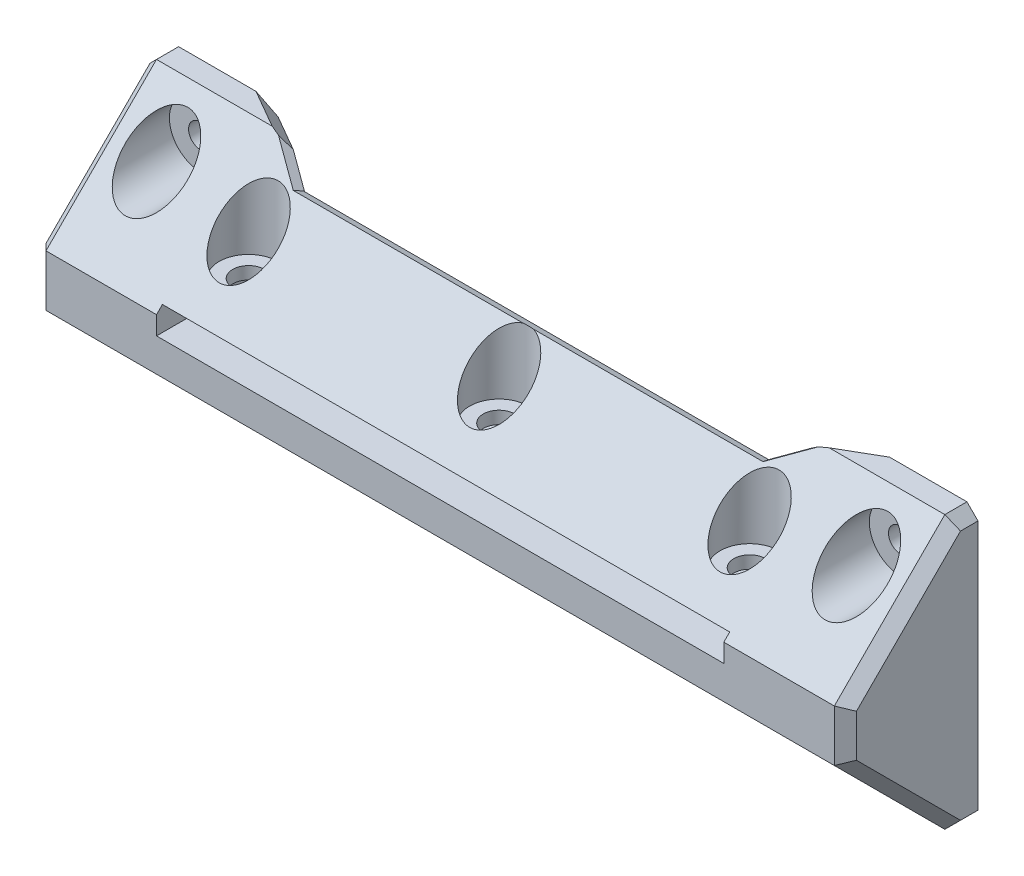
SolidWorks part; units mm, degrees
ref_plane "Front Plane" through (0, 0, 0) normal (0, 0, 1) x (1, 0, 0)
ref_plane "Top Plane" through (0, 0, 0) normal (0, 1, 0) x (1, 0, 0)
ref_plane "Right Plane" through (0, 0, 0) normal (1, 0, 0) x (0, 0, -1)
sketch "Sketch1" plane through (0, 0, 0) normal (0, 0, 1) x (1, 0, 0)
  line L1 (-102.5, 51) -> (7.5, 51)
  line L2 (-102.5, 51) -> (-102.5, 14)
  line L3 (-102.5, 14) -> (7.5, 14)
  line L4 (7.5, 51) -> (7.5, 14)
  line L8 (-9.0001, 36.8) -> (-85.9999, 36.8)
  line L9 (-9.0001, 36.8) -> (-9.0001, 33.5)
  line L10 (-9.0001, 33.5) -> (-85.9999, 33.5)
  line L11 (-85.9999, 36.8) -> (-85.9999, 33.5)
  line L12 (-10.0001, 34) -> (-13.5, 34) construction
  line L14 (-84.9999, 37) -> (-84.9999, 34) construction
  line L15 (-10.0001, 37) -> (-10.0001, 34) construction
  line L16 (-78.5, 37) -> (-16.5, 37) construction
  line L17 (7.5, 29.6539) -> (7.5, 84.2824) construction
  line L18 (-102.5, 18.739) -> (-102.5, -23.6652) construction
  arc A0 (-95, 46.65) -> (-95, 43.35) centre (-95, 45) ccw construction
  arc A1 (-95, 43.35) -> (-95, 46.65) centre (-95, 45) ccw construction
  arc A2 (0, 46.65) -> (0, 43.35) centre (0, 45) ccw construction
  arc A3 (0, 43.35) -> (0, 46.65) centre (0, 45) ccw construction
  arc A4 (0, 21.65) -> (0, 18.35) centre (0, 20) ccw construction
  arc A5 (0, 18.35) -> (0, 21.65) centre (0, 20) ccw construction
  arc A6 (-95, 21.65) -> (-95, 18.35) centre (-95, 20) ccw construction
  arc A7 (-95, 18.35) -> (-95, 21.65) centre (-95, 20) ccw construction
  arc A8 (-95, 18.35) -> (-95, 21.65) centre (-95, 20) ccw
  arc A9 (-95, 21.65) -> (-95, 18.35) centre (-95, 20) ccw
  arc A10 (0, 18.35) -> (0, 21.65) centre (0, 20) ccw
  arc A11 (0, 21.65) -> (0, 18.35) centre (0, 20) ccw
  arc A12 (0, 43.35) -> (0, 46.65) centre (0, 45) ccw
  arc A13 (0, 46.65) -> (0, 43.35) centre (0, 45) ccw
  arc A14 (-95, 43.35) -> (-95, 46.65) centre (-95, 45) ccw
  arc A15 (-95, 46.65) -> (-95, 43.35) centre (-95, 45) ccw
  dimension "D5" = 6
  dimension "D1" = 0.2
  dimension "D2" = 0.5
  dimension "D3" = 1
  dimension "D4" = 1
  dimension "D6" = 6
extrude "Extrude1" add sketch "Sketch1" along normal blind 18
chamfer "Chamfer1" distance 15 angle 45 2 edges at (-47.5, 14, 18) (-47.5, 51, 18)
ref_plane "Plane1" through (0, 0, 3) normal (0, 0, -1) x (-1, 0, 0)
sketch "Sketch3" plane through (0, 0, 3) normal (0, 0, -1) x (-1, 0, 0)
  circle A4 centre (0, 20) radius 4.25
  circle A5 centre (95, 20) radius 4.25
  circle A6 centre (0, 45) radius 4.25
  circle A7 centre (95, 45) radius 4.25
  dimension "D1" = 8.5
  dimension "D2" = 8.5
  dimension "D3" = 8.5
  dimension "D4" = 8.5
extrude "Cut-Extrude1" cut sketch "Sketch3" against normal blind 18
sketch "Sketch4" plane through (0, 36.8, 0) normal (0, -1, 0) x (1, 0, 0)
  line L0 (-13.5001, 10) -> (-81.4999, 10) construction
  line L2 (7.5, 0) -> (-102.5, 0) construction
  line L4 (-102.5, 18) -> (-102.5, 3) construction
  line L5 (7.5, 3) -> (7.5, 18) construction
  circle A0 centre (-13.5001, 10) radius 2.15
  circle A1 centre (-81.4999, 10) radius 2.15
  circle A2 centre (-47.5, 10) radius 2.15
  dimension "D1" = 21.0001
  dimension "D2" = 21.0001
  dimension "D3" = 4.3
  dimension "D4" = 10
extrude "Cut-Extrude2" cut sketch "Sketch4" against normal blind 19
sketch "Sketch5" plane through (0, 33.5, 0) normal (0, 1, 0) x (1, 0, 0)
  circle A0 centre (-81.4999, -10) radius 1.75
  circle A1 centre (-47.5, -10) radius 1.75
  circle A2 centre (-13.5001, -10) radius 1.75
  dimension "D1" = 3.5
extrude "Cut-Extrude3" cut sketch "Sketch5" against normal blind 19
ref_plane "Plane2" through (0, 38.5, 0) normal (0, 1, 0) x (1, 0, 0)
sketch "Sketch6" plane through (0, 38.5, 0) normal (0, 1, 0) x (1, 0, 0)
  circle A0 centre (-81.4999, -10) radius 4
  circle A1 centre (-47.5, -10) radius 4
  circle A2 centre (-13.5001, -10) radius 4
  dimension "D1" = 8
extrude "Cut-Extrude4" cut sketch "Sketch6" along normal blind 41
sketch "Sketch7" plane through (0, 51, 0) normal (0, 1, 0) x (1, 0, 0)
  line L0 (-87.5, 0) -> (-78.8397, -5)
  line L1 (7.5, 0) -> (-102.5, 0) construction
  line L2 (-87.5, 0) -> (-92.5, 0) construction
  line L3 (-78.8397, -5) -> (-16.1603, -5)
  line L4 (-16.1603, -5) -> (-7.5, 0)
  line L5 (-2.5, 0) -> (-7.5, 0) construction
  line L6 (-7.5, 0) -> (-87.5, 0)
  line L7 (-7.5, 3) -> (-7.5, 0) construction
  line L8 (-87.5, 3) -> (-87.5, 0) construction
  point P6 (-7.5, 0)
  point P13 (-87.5, 0)
  dimension "D1" = 30
  dimension "D2" = 30
  dimension "D3" = 5
extrude "Cut-Extrude5" cut sketch "Sketch7" against normal blind 50
chamfer "Chamfer2" distance 1.5 10 edges at (-84.9019, 14, 1.5) (-80.5718, 15, 4) (-47.5, 16, 5) (-14.4282, 15, 4) (-10.0981, 14, 1.5) (-84.9019, 51, 1.5) (-80.5718, 50, 4) (-10.0981, 51, 1.5) (-14.4282, 50, 4) (-47.5, 49, 5)
chamfer "Chamfer4" distance 1.5 10 edges at (7.5, 14, 1.5) (7.5, 51, 1.5) (7.5, 43.5, 10.5) (7.5, 21.5, 10.5) (7.5, 32.5, 18) (-102.5, 14, 1.5) (-102.5, 21.5, 10.5) (-102.5, 51, 1.5) (-102.5, 43.5, 10.5) (-102.5, 32.5, 18)
